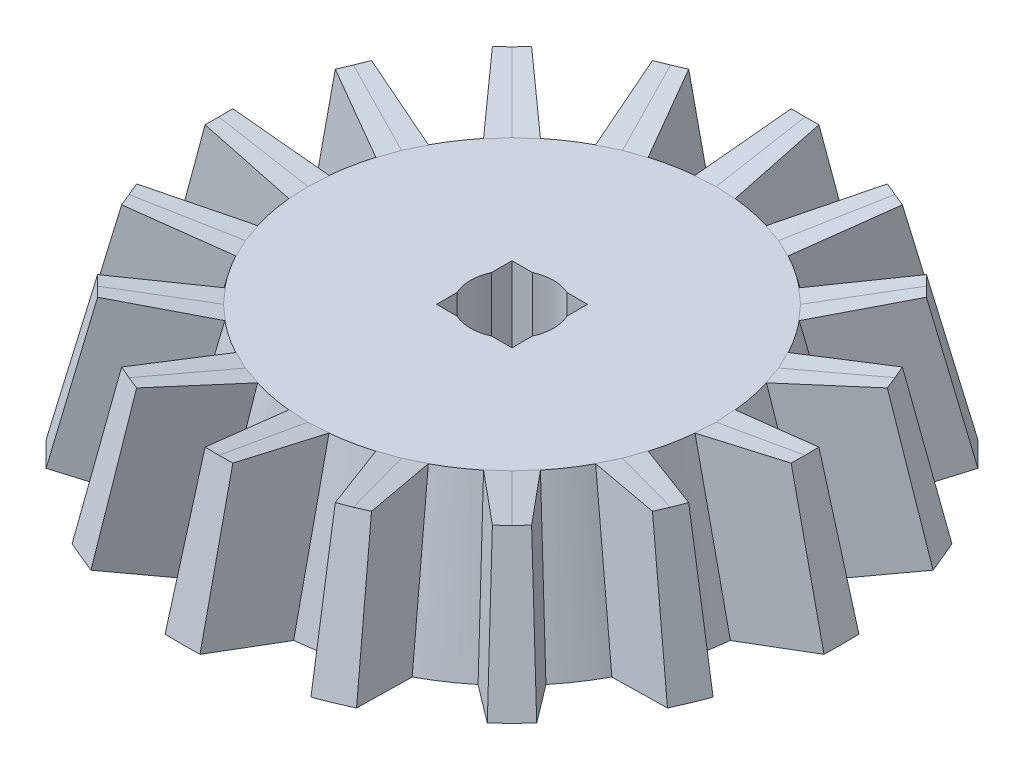
SolidWorks part; units mm, degrees
material "ABS"
ref_plane "Front Plane" through (0, 0, 0) normal (0, 0, 1) x (1, 0, 0)
ref_plane "Top Plane" through (0, 0, 0) normal (0, 1, 0) x (1, 0, 0)
ref_plane "Right Plane" through (0, 0, 0) normal (1, 0, 0) x (0, 0, -1)
sketch "Sketch1" plane through (0, 0, 0) normal (0, 0, 1) x (1, 0, 0)
  line L0 (0, 0) -> (10.264, 0)
  line L1 (10.264, 0) -> (8.5998, 6.6551)
  line L2 (8.5998, 6.6551) -> (0, 6.6551)
  line L3 (0, 6.6551) -> (0, 0)
  dimension "D1" = 10.264
  dimension "D2" = 75.96
  dimension "D3" = 6.86
revolve "Revolve1" add sketch "Sketch1" angle 360 about L3
sketch "Sketch2" plane through (0, 0, 0) normal (0, 0, 1) x (1, 0, 0)
  line L0 (0, 0) -> (0, 67.611) construction
  line L1 (0, 67.611) -> (0, -92.6067) construction
sketch "Sketch3" plane through (0, 0, 0) normal (1, 0, 0) x (0, 0, -1)
  line L0 (-10.264, 0) -> (-8.5998, 6.6551) construction
  line L1 (-8.5998, 6.6551) -> (0, 41.0446) construction
  line L2 (0, 67.611) -> (0, -92.6067) construction
  line L3 (0, 41.0446) -> (-39.1729, -115.6035) construction
ref_plane "Plane1" through (0, 2.4157, 9.6599) normal (0, 0.2426, 0.9701) x (1, 0, 0)
sketch "Sketch8" plane through (0, 2.4157, 9.6599) normal (0, 0.2426, 0.9701) x (1, 0, 0)
  line L0 (0, 4.37) -> (0.8443, 4.38)
  line L1 (0.8443, 4.38) -> (1.0077, -2.478)
  line L2 (1.0077, -2.478) -> (0, -2.49)
  line L3 (0, -2.49) -> (-1.0077, -2.478)
  line L4 (-1.0077, -2.478) -> (-0.8443, 4.38)
  line L5 (-0.8443, 4.38) -> (0, 4.37)
  ellipse E0 centre (0, 6.4563) end of major axis (8.5998, 6.4563) minor radius 2.0863 construction
  ellipse E1 centre (0, 0) end of major axis (10.264, 0) minor radius 2.49 construction
  dimension "D1" = 1.0077
  dimension "D2" = 1.0077
  dimension "D3" = 0.8443
  dimension "D4" = 0.8443
extrude "Boss-Extrude1" add sketch "Sketch8" along normal blind 3.8 draft 4 and the other way blind 0.1 draft 4 other way draft outward yes
pattern_circular "CirPattern5" count 16 over 360 about axis through (0, 67.611, 0) along (0, -1, 0) of "Boss-Extrude1"
sketch "Sketch9" plane through (0, 6.6551, 0) normal (0, 1, 0) x (1, 0, 0)
  circle A0 centre (0, 0) radius 1.75
  dimension "D1" = 3.5
extrude "Cut-Extrude1" cut sketch "Sketch9" against normal blind 11.5
sketch "Sketch10" plane through (0, 0, 0) normal (0, 1, 0) x (1, 0, 0)
  line L1 (-1.59, 1.59) -> (1.59, 1.59)
  line L2 (-1.59, 1.59) -> (-1.59, -1.59)
  line L3 (-1.59, -1.59) -> (1.59, -1.59)
  line L4 (1.59, 1.59) -> (1.59, -1.59)
  line L5 (-1.59, 1.59) -> (1.59, -1.59) construction
  line L6 (-1.59, -1.59) -> (1.59, 1.59) construction
  point P0 (0, 0)
  dimension "D1" = 3.18
  dimension "D2" = 3.18
extrude "Cut-Extrude3" cut sketch "Sketch10" along normal blind 10
sketch "Sketch11" plane through (0, 0, 0) normal (0, -1, 0) x (1, 0, 0)
  circle A0 centre (0, 0) radius 13.97
extrude "Cut-Extrude4" cut sketch "Sketch11" along normal blind 10
